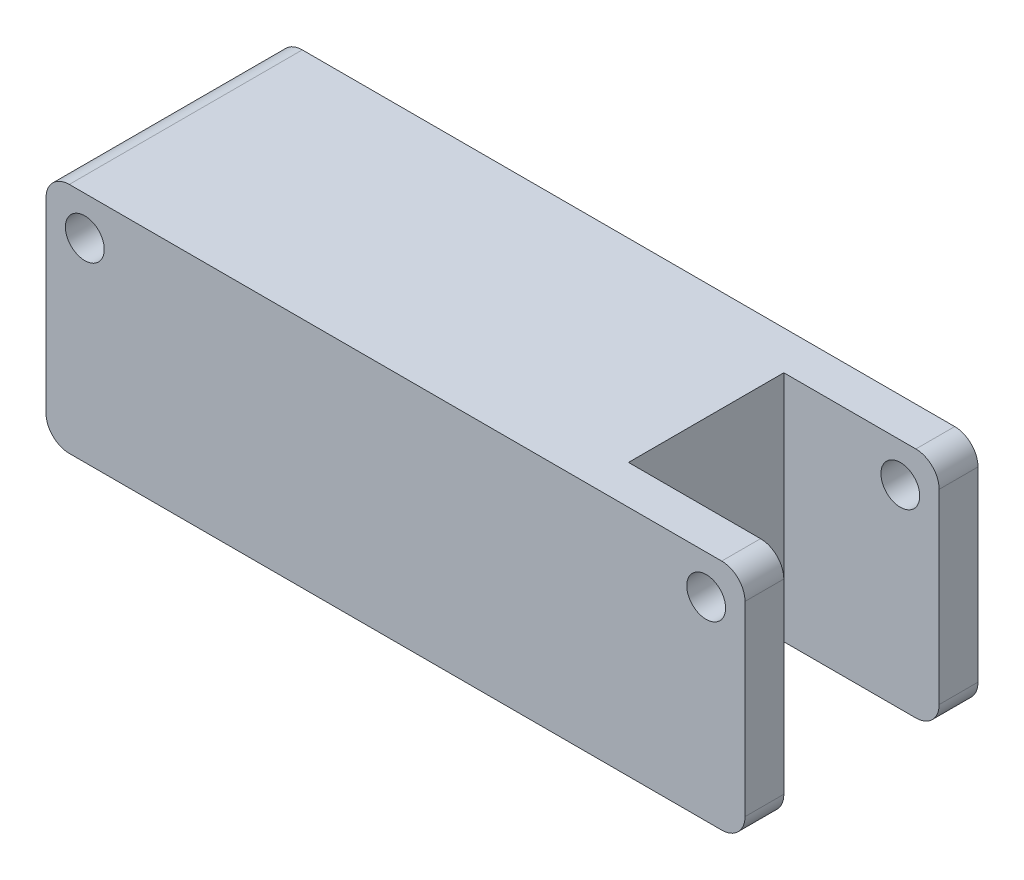
SolidWorks part; units mm, degrees
ref_plane "Plan de face" through (0, 0, 0) normal (0, 0, 1) x (1, 0, 0)
ref_plane "Plan de dessus" through (0, 0, 0) normal (0, 1, 0) x (1, 0, 0)
ref_plane "Plan de droite" through (0, 0, 0) normal (1, 0, 0) x (0, 0, -1)
other "Centre de masse"
sketch "Esquisse2" plane through (0, 0, 0) normal (0, 1, 0) x (1, 0, 0)
  line L0 (0, 0) -> (56.0293, 0) construction
  line L1 (0, -15) -> (90, -15)
  line L2 (0, -15) -> (0, 15)
  line L3 (0, 15) -> (90, 15)
  line L4 (90, -15) -> (90, 15)
  line L5 (0, 0) -> (0, -42.7765) construction
  dimension "D1" = 90
  dimension "D2" = 30
extrude "Boss.-Extru.1" add sketch "Esquisse2" along normal mid plane 30
fillet "Congé1" radius 3 4 edges at (0, 15, 0) (90, 15, 0) (90, -15, 0) (0, -15, 0)
sketch "Esquisse4" plane through (0, 15, 0) normal (0, 1, 0) x (1, 0, 0)
  line L0 (90, 15) -> (90, -15) construction
  line L1 (90, 10) -> (90, -10)
  line L2 (90, -10) -> (70, -10)
  line L4 (70, -10) -> (70, 10)
  line L6 (70, 10) -> (90, 10)
  line L7 (3, -15) -> (87, -15) construction
  line L8 (63.6485, 0) -> (81.8664, 0) construction
  dimension "D1" = 20
  dimension "D2" = 5
extrude "Enlèv. mat.-Extru.1" cut sketch "Esquisse4" against normal through all
sketch "Esquisse5" plane through (0, 0, -15) normal (0, 0, -1) x (-1, 0, 0)
  line L0 (-87, 15) -> (-3, 15) construction
  line L1 (-90, 12) -> (-90, -12) construction
  line L2 (-45, 0) -> (-45, 9.0949) construction
  circle A0 centre (-85, 10) radius 2.5
  circle A1 centre (-5, 10) radius 2.5
  dimension "D1" = 5
  dimension "D2" = 5
  dimension "D3" = 5
  dimension "D4" = 45
extrude "Enlèv. mat.-Extru.2" cut sketch "Esquisse5" against normal through all
ref_axis "Axe1" through (5, 10, 15) along (0, 0, -1)
ref_point "Point1"
ref_axis "Axe2" through (85, 10, 15) along (0, 0, -1)
ref_point "Point2"
equation "\"L\"= 0.03m"
equation "\"ldoigt\"= 0.09m"
equation "\"D1@Esquisse2\"=\"ldoigt\""
equation "\"D2@Esquisse2\"=\"L\""
equation "\"e\"= 0.03m"
equation "\"D1@Congé1\"=\"e\"/10m"
equation "\"D4@Esquisse5\"=\"ldoigt\"/2"
